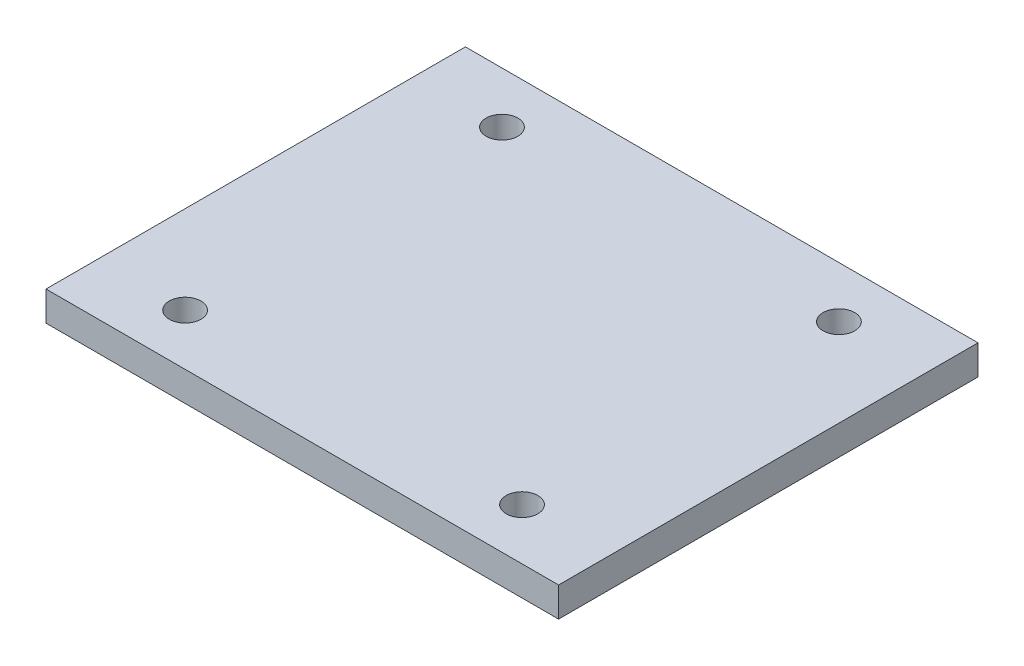
SolidWorks part; units mm, degrees
ref_plane "Front Plane" through (0, 0, 0) normal (0, 0, 1) x (1, 0, 0)
ref_plane "Top Plane" through (0, 0, 0) normal (0, 1, 0) x (1, 0, 0)
ref_plane "Right Plane" through (0, 0, 0) normal (1, 0, 0) x (0, 0, -1)
sketch "Sketch2" plane through (0, 0, 0) normal (0, 1, 0) x (1, 0, 0)
  line L0 (0, 0) -> (0, 90)
  line L1 (0, 90) -> (110, 90)
  line L2 (110, 90) -> (110, 0)
  line L3 (110, 0) -> (0, 0)
  dimension "D1" = 110
  dimension "D2" = 90
extrude "Boss-Extrude1" add sketch "Sketch2" along normal blind 6.35
sketch "Sketch3" plane through (0, 6.35, 0) normal (0, 1, 0) x (1, 0, 0)
  line L1 (110, 90) -> (0, 90) construction
  line L2 (0, 0) -> (110, 0) construction
  line L4 (55, 90) -> (55, 0) construction
  line L5 (0, 45) -> (55, 45) construction
  line L6 (55, 45) -> (110, 45) construction
  line L7 (0, 90) -> (0, 0) construction
  circle A0 centre (18.85, 79) radius 3.4
  circle A1 centre (18.85, 11) radius 3.4
  circle A2 centre (91.15, 11) radius 3.4
  circle A3 centre (91.15, 79) radius 3.4
  dimension "D4" = 6.8
  dimension "D3" = 11
  dimension "D2" = 18.85
extrude "Mounting Holes" cut sketch "Sketch3" against normal through all
equation "\"L1L\"=500"
equation "\"L1Thick\"=6.35"
equation "\"Harm-Drive-Outer\"=74.5"
equation "\"L1-Spacing\"=100"
equation "\"L-Bracket-HoleToWall\"=12.5"
equation "\"D3@Sketch3\"=\"L-Bracket-HoleToSide\""
equation "\"L-Bracket-HoleToSide\"=11"
equation "\"Bracket-Hole-D\"=6.8"
equation "\"D4@Sketch3\"=\"Bracket-Hole-D\""
equation "\"L1-Spacing\"=115.65"
equation "\"D2@Sketch3\"=\"L-Bracket-HoleToWall\"+\"L1Thick\""
